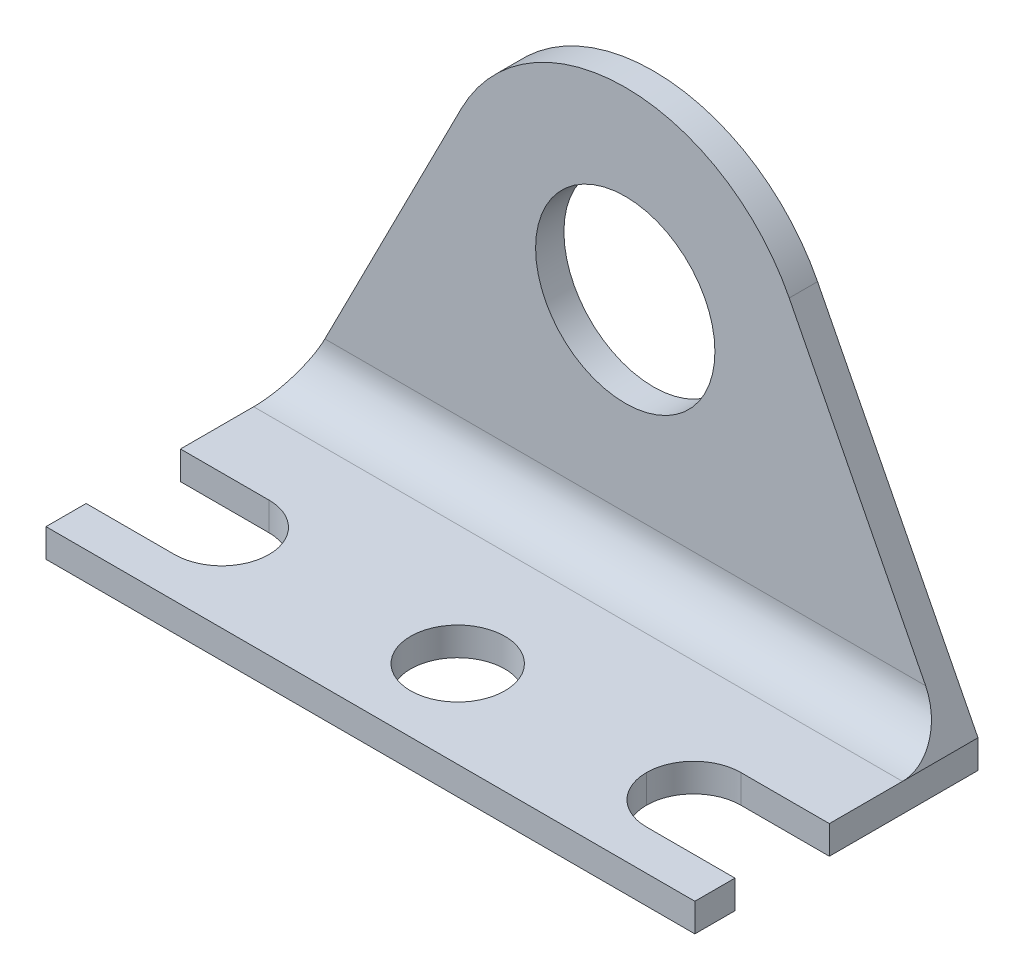
SolidWorks part; units mm, degrees
note: '?' marks a value the reader was unsure of.
ref_plane "Front" through (0, 0, 0) normal (0, 0, 1) x (1, 0, 0)
ref_plane "Top" through (0, 0, 0) normal (0, 1, 0) x (1, 0, 0)
ref_plane "Right" through (0, 0, 0) normal (1, 0, 0) x (0, 0, -1)
sketch "Sketch1" plane through (0, 0, 0) normal (0, 0, 1) x (1, 0, 0)
  line L0 (0, 0) -> (0, 76.308) construction
  line L1 (-17.4625, 0) -> (17.4625, 0)
  line L2 (17.4625, 0) -> (17.4625, 1.524)
  line L3 (-17.4625, 0) -> (-17.4625, 1.524)
  line L4 (17.4625, 1.524) -> (8.8256, 18.4685)
  line L5 (-17.4625, 1.524) -> (-8.8256, 18.4685)
  arc A0 (8.8256, 18.4685) -> (0, 23.876) centre (0, 13.97) ccw
  arc A1 (-8.8256, 18.4685) -> (0, 23.876) centre (0, 13.97) cw
  circle A2 centre (0, 13.97) radius 4.826
  dimension "D1" = 9.906
  dimension "D5" = 9.652
  dimension "D2" = 34.925
  dimension "D3" = 1.524
  dimension "D4" = 13.97
extrude "Extrude1" add sketch "Sketch1" along normal blind 1.524
sketch "Sketch2" plane through (0, 0, 0) normal (0, 0, -1) x (-1, 0, 0)
  line L0 (17.4625, 0) -> (-17.4625, 0) construction
  line L1 (17.4625, 0) -> (-17.4625, 0)
  line L2 (-17.4625, 0) -> (-17.4625, 1.524) construction
  line L3 (-17.4625, 0) -> (-17.4625, 1.524)
  line L4 (17.4625, 1.524) -> (17.4625, 0) construction
  line L5 (17.4625, 1.524) -> (17.4625, 0)
  line L6 (17.4625, 1.524) -> (-17.4625, 1.524)
extrude "Extrude2" add sketch "Sketch2" against normal blind 15.24
sketch "Sketch3" plane through (0, 1.524, 0) normal (0, 1, 0) x (-1, 0, 0)
  line L0 (0, 10.541) -> (0, 15.24) construction
  line L1 (0, 0) -> (0, 10.541) construction
  line L2 (17.4625, 15.24) -> (-17.4625, 15.24) construction
  circle A0 centre (0, 10.541) radius 2.54
  dimension "D1" = 5.08
  dimension "D2" = 4.699
extrude "Cut-Extrude1" cut sketch "Sketch3" against normal through all
sketch "Sketch4" plane through (0, 1.524, 0) normal (0, 1, 0) x (-1, 0, 0)
  line L0 (0, 10.541) -> (17.4625, 10.541) construction
  line L1 (17.4625, 15.24) -> (17.4625, 1.524) construction
  line L2 (17.4625, 8.001) -> (12.7, 8.001)
  line L3 (17.4625, 13.081) -> (12.7, 13.081)
  arc A0 (12.7, 8.001) -> (10.16, 10.541) centre (12.7, 10.541) cw
  arc A1 (12.7, 13.081) -> (10.16, 10.541) centre (12.7, 10.541) ccw
  dimension "D1" = 2.54
  dimension "D2" = 12.7
extrude "Cut-Extrude2" cut sketch "Sketch4" against normal through all and the other way through all
mirror "Mirror1" about plane through (0, 0, 0) normal (1, 0, 0)
fillet "Fillet1" radius 2.54
ref_axis "Axis1" through (-12.7, 0, 10.541) along (0, 1, 0)?
ref_axis "Axis2" through (12.7, 0, 10.541) along (0, 1, 0)?
